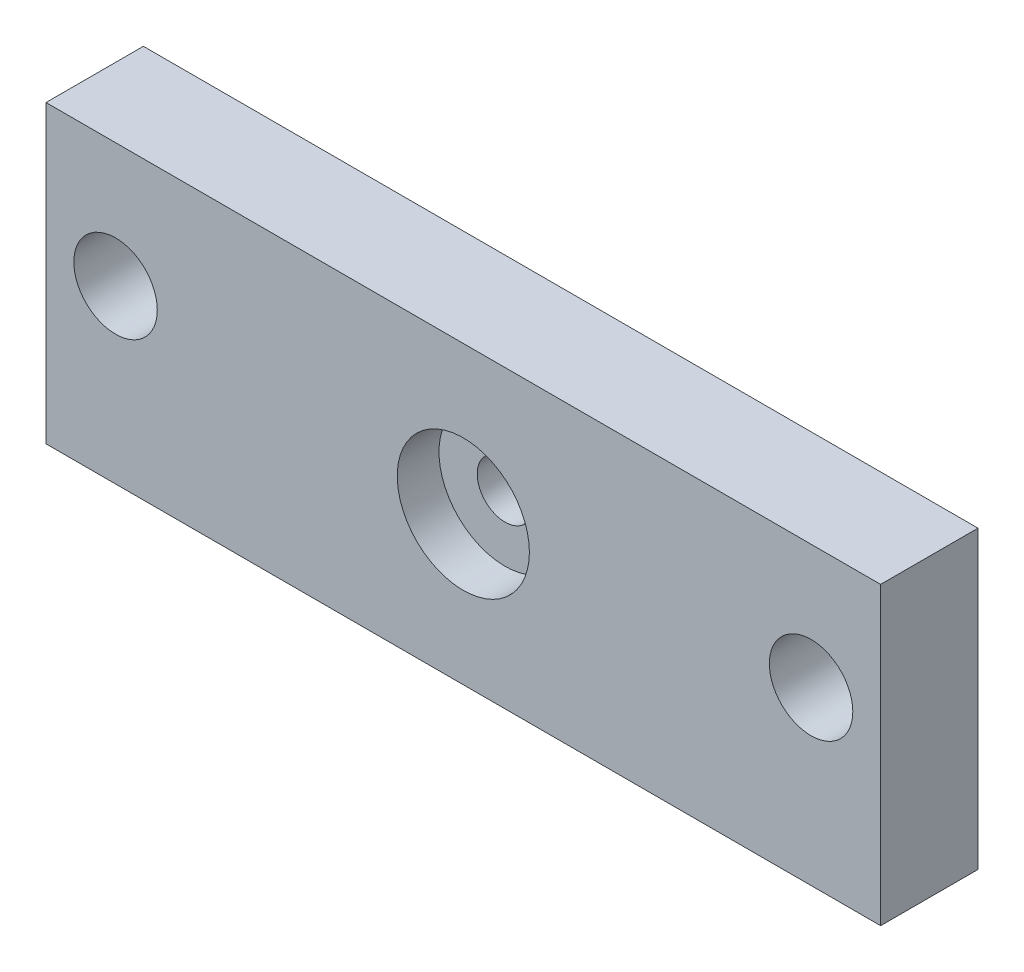
SolidWorks part; units mm, degrees
ref_plane "Front Plane" through (0, 0, 0) normal (0, 0, 1) x (1, 0, 0)
ref_plane "Top Plane" through (0, 0, 0) normal (0, 1, 0) x (1, 0, 0)
ref_plane "Right Plane" through (0, 0, 0) normal (1, 0, 0) x (0, 0, -1)
sketch "Sketch1" plane through (0, 0, 0) normal (0, 0, 1) x (1, 0, 0)
  line L1 (-60, -21.25) -> (60, -21.25)
  line L2 (-60, -21.25) -> (-60, 21.25)
  line L3 (-60, 21.25) -> (60, 21.25)
  line L4 (60, -21.25) -> (60, 21.25)
  line L5 (-60, -21.25) -> (60, 21.25) construction
  line L6 (-60, 21.25) -> (60, -21.25) construction
  point P0 (0, 0)
  dimension "D1" = 120
  dimension "D2" = 42.5
extrude "Boss-Extrude1" add sketch "Sketch1" along normal mid plane 14
sketch "Sketch2" plane through (0, 0, 7) normal (0, 0, 1) x (1, 0, 0)
  circle A0 centre (0, 0) radius 9.5
  dimension "D1" = 19
extrude "Cut-Extrude1" cut sketch "Sketch2" against normal blind 6
sketch "Sketch3" plane through (0, 0, 1) normal (0, 0, 1) x (1, 0, 0)
  circle A0 centre (0, 0) radius 4
  dimension "D1" = 8
extrude "Cut-Extrude2" cut sketch "Sketch3" against normal through all
sketch "Sketch5" plane through (0, 0, 7) normal (0, 0, 1) x (1, 0, 0)
  line L0 (-40.6477, 3.4) -> (36.4799, 3.4) construction
  circle A0 centre (-50, 3.4) radius 6
  circle A1 centre (50, 3.4) radius 6
  dimension "D1" = 12
  dimension "D2" = 12
  dimension "D4" = 50
  dimension "D3" = 50
  dimension "D5" = 3.4
extrude "Cut-Extrude4" cut sketch "Sketch5" against normal through all
sketch "Sketch6" plane through (0, -21.25, 0) normal (0, -1, 0) x (1, 0, 0)
  line L0 (-60, 0) -> (60, 0) construction
  line L1 (-60, 7) -> (-60, -7) construction
  line L2 (60, 7) -> (60, -7) construction
  circle A0 centre (-50, 0) radius 2.1
  circle A1 centre (-25, 0) radius 2.1
  circle A2 centre (25, 0) radius 2.1
  circle A3 centre (50, 0) radius 2.1
  circle A4 centre (-37.5, 0) radius 1.25
  circle A5 centre (37.5, 0) radius 1.25
  dimension "D1" = 4.2
  dimension "D2" = 4.2
  dimension "D3" = 4.2
  dimension "D4" = 4.2
  dimension "D5" = 10
  dimension "D9" = 2.5
  dimension "D10" = 2.5
  dimension "D11" = 22.5
  dimension "D12" = 22.5
  dimension "D6" = 35
  dimension "D7" = 10
  dimension "D8" = 35
extrude "Cut-Extrude5" cut sketch "Sketch6" against normal blind 10
